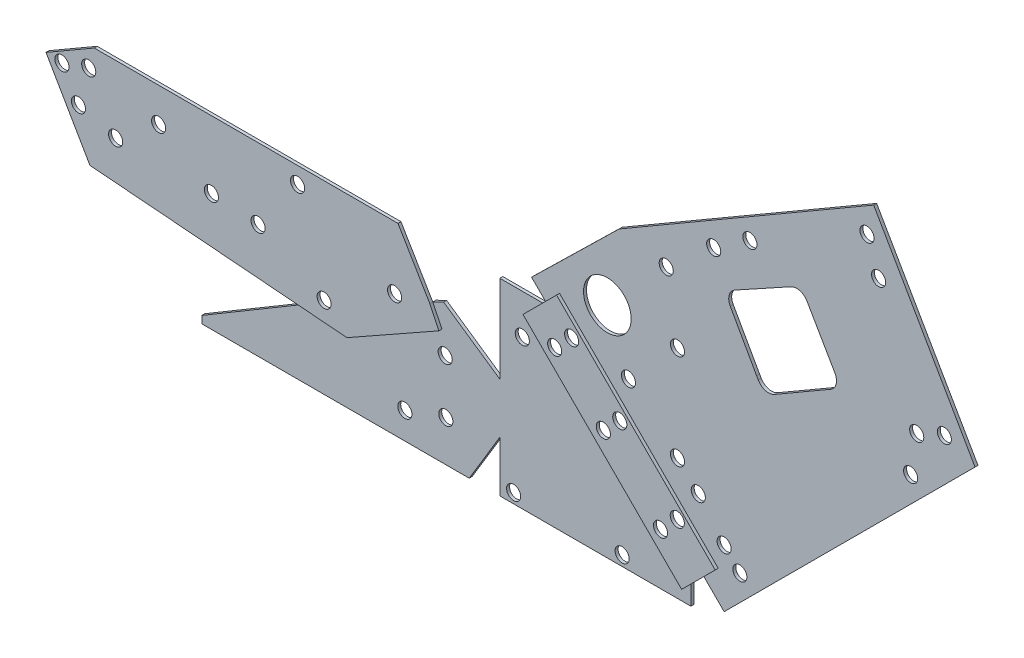
SolidWorks part; units mm, degrees
ref_plane "Plano frontal" through (0, 0, 0) normal (0, 0, 1) x (1, 0, 0)
ref_plane "Plano superior" through (0, 0, 0) normal (0, 1, 0) x (1, 0, 0)
ref_plane "Plano direito" through (0, 0, 0) normal (1, 0, 0) x (0, 0, -1)
sketch "Esboço1" plane through (0, 0, 0) normal (0, 0, 1) x (1, 0, 0)
  line L0 (341.3333, 723.5) -> (1706.6667, 723.5) construction
  line L1 (4933.5577, 4260.6978) -> (5445.3782, 3370.7776)
  line L2 (5445.3782, 3370.7776) -> (4178.4392, 2104.8716)
  line L3 (4178.4392, 2104.8716) -> (4076.0051, 2207.3893)
  line L4 (4076.0051, 2207.3893) -> (4148.4155, 2279.7406)
  line L5 (4148.4155, 2279.7406) -> (3347.2308, 3081.579)
  line L6 (3347.2308, 3081.579) -> (3177.5814, 2912.0679)
  line L7 (3177.5814, 2912.0679) -> (3978.7661, 2110.2295)
  line L8 (3978.7661, 2110.2295) -> (4076.0051, 2207.3893)
  line L9 (3276.4892, 3010.8951) -> (3205.8629, 3081.579)
  line L10 (3205.8629, 3081.579) -> (3647.9072, 3513.3999)
  line L11 (3647.9072, 3513.3999) -> (4100.6528, 3776.9135)
  line L12 (4100.6528, 3776.9135) -> (4933.5577, 4260.6978)
  line L13 (3262.4061, 2996.8235) -> (3045.3808, 2996.8235)
  line L14 (3045.3808, 2996.8235) -> (3045.3808, 2044.886)
  line L15 (3045.3808, 2044.886) -> (4010.5334, 2044.886)
  line L16 (4010.5334, 2044.886) -> (4010.5334, 2141.9709)
  line L17 (2890.9478, 2044.886) -> (3045.3808, 2300.8767)
  line L18 (3045.3808, 2555.7255) -> (2762.0065, 2750.4853)
  line L19 (2762.0065, 2750.4853) -> (2706.993, 2724.0231)
  line L20 (2706.993, 2724.0231) -> (2753.1477, 2628.0699)
  line L21 (2753.1477, 2628.0699) -> (2288.4358, 2365.9015)
  line L22 (2288.4358, 2365.9015) -> (990.6315, 2470.3434)
  line L23 (990.6315, 2470.3434) -> (768.8685, 2853.6686)
  line L24 (768.8685, 2853.6686) -> (1012.6244, 2994.6873)
  line L25 (1012.6244, 2994.6873) -> (2546.3196, 2994.6873)
  line L26 (2546.3196, 2994.6873) -> (2706.993, 2724.0231)
  line L27 (1540.7391, 2044.886) -> (1540.7391, 2081.8221)
  line L28 (1540.7391, 2081.8221) -> (2051.4198, 2384.9756)
  line L29 (1540.7391, 2044.886) -> (2890.9478, 2044.886)
  line L30 (4342.3927, 3218.7645) -> (4216.4124, 3443.6797)
  line L31 (4238.4239, 3541.7347) -> (4515.798, 3694.658)
  line L32 (4596.6793, 3672.1987) -> (4737.9418, 3428.439)
  line L33 (4716.1132, 3346.4419) -> (4432.8719, 3182.2993)
  line L34 (4342.3927, 3218.7645) -> (4350.8749, 3204.1279)
  line L35 (4238.4239, 3541.7347) -> (4232.5399, 3538.4907)
  line L36 (4216.4124, 3443.6797) -> (4209.1608, 3456.626)
  circle A0 centre (3588.5895, 3150.4639) radius 120.3133
  circle A1 centre (4899.7093, 4116.2578) radius 35.6606
  circle A2 centre (4958.2142, 3952.2718) radius 35.6606
  circle A3 centre (5150.8633, 3370.7776) radius 35.6606
  circle A4 centre (5290.3818, 3431.5246) radius 35.6606
  circle A5 centre (5120.2839, 3175.4222) radius 35.6606
  circle A6 centre (4308.3601, 3792.9081) radius 35.6606
  circle A7 centre (4125.661, 3670.6609) radius 35.6606
  circle A8 centre (4257.693, 2313.3917) radius 35.6606
  circle A9 centre (4178.4392, 2396.3217) radius 35.6606
  circle A10 centre (4047.7765, 2555.7255) radius 35.6606
  circle A11 centre (3942.8183, 2659.3652) radius 35.6606
  circle A12 centre (3695.1216, 2881.1287) radius 35.6606
  circle A13 centre (3942.8183, 3140.5478) radius 35.6606
  circle A14 centre (3885.941, 3466.2564) radius 35.6606
  circle A15 centre (3956.7376, 2405.3029) radius 35.6606
  circle A16 centre (3872.0513, 2319.6318) radius 35.6606
  circle A17 centre (3583.4304, 2608.084) radius 35.6606
  circle A18 centre (3666.3262, 2690.9798) radius 35.6606
  circle A19 centre (3337.5538, 2847.9017) radius 35.6606
  circle A20 centre (3423.381, 2932.3447) radius 35.6606
  circle A21 centre (3159.0283, 2796.0426) radius 35.6606
  circle A22 centre (3115.3836, 2094.8055) radius 35.6606
  circle A23 centre (3663.3337, 2096.1195) radius 35.6606
  circle A24 centre (2565.9127, 2179.6694) radius 35.6606
  circle A25 centre (2769.7856, 2520.4665) radius 35.6606
  circle A26 centre (2772.8644, 2251.0772) radius 35.6606
  circle A27 centre (2173.1952, 2472.0856) radius 35.6606
  circle A28 centre (2529.1931, 2678.1099) radius 35.6606
  circle A29 centre (1604.09, 2654.1286) radius 35.6606
  circle A30 centre (1839.8326, 2636.6662) radius 35.6606
  circle A31 centre (2039.3115, 2911.4571) radius 35.6606
  circle A32 centre (1120.5017, 2654.4881) radius 35.6606
  circle A33 centre (1337.6956, 2822.5846) radius 35.6606
  circle A34 centre (984.5932, 2893.1951) radius 35.6606
  circle A35 centre (849.4236, 2847.1799) radius 35.6606
  circle A36 centre (932.8261, 2706.2585) radius 35.6606
  arc A37 (4350.8749, 3204.1279) -> (4432.8719, 3182.2993) centre (4402.7877, 3234.2121) ccw
  arc A38 (4737.9418, 3428.439) -> (4716.1132, 3346.4419) centre (4686.029, 3398.3547) cw
  arc A39 (4596.6793, 3672.1987) -> (4515.798, 3694.658) centre (4544.7665, 3642.1145) ccw
  arc A40 (4209.1608, 3456.626) -> (4232.5399, 3538.4907) centre (4261.5084, 3485.9472) cw
  point P116 (4380.9591, 3152.2151)
  dimension "D28" = 60
  dimension "D1" = 1026.6052
  dimension "D2" = 1790.992
  dimension "D3" = 144.9228
  dimension "D4" = 99.9215
  dimension "D5" = 617.9583
  dimension "D6" = 239.8227
  dimension "D7" = 1133.5086
  dimension "D8" = 523.8492
  dimension "D9" = 963.2122
  dimension "D10" = 217.0253
  dimension "D11" = 951.9375
  dimension "D12" = 965.1526
  dimension "D13" = 97.085
  dimension "D14" = 298.9663
  dimension "D15" = 343.8494
  dimension "D16" = 61.047
  dimension "D17" = 106.4767
  dimension "D18" = 533.563
  dimension "D19" = 1302
  dimension "D20" = 442.8511
  dimension "D21" = 281.6083
  dimension "D22" = 1533.6952
  dimension "D23" = 314.7619
  dimension "D24" = 36.9362
  dimension "D25" = 593.8829
  dimension "D26" = 1350.2087
  dimension "D27" = 257.7943
extrude "Ressalto-extrusão1" add sketch "Esboço1" along normal blind 15 contours L7 L8 L4 L5 L6 A20 A19 A18 A17 A16 A15 region at (3665.2309, 2592.2162, 0)
extrude "Ressalto-extrusão2" add sketch "Esboço1<3>" against normal blind 15 separate body contours L12 L11 L10 L9 L6 L5 L4 L3 L2 L1 A14 A13 A12 A11 A10 A9 A8 A7 A6 A5 A4 A3 A2 A1 A0 L36 A40 L35 L31 A39 L32 A38 L33 A37 L34 | L15 L16 L8 L7 L6 L13 L14 A23 A22 A21 | L27 L29 L17 L14 L18 L19 L20 L21 L22 L28 A26 A25 A24 region at (5162.5213, 3800.2399, 0) region at (3378.2113, 2386.2015, 0) region at (2463.1151, 2278.2783, 0)
sketch "Esboço1<3>" plane through (0, 0, 0) normal (0, 0, 1) x (1, 0, 0) same geometry as "Esboço1"
extrude "Ressalto-extrusão3" add sketch "Esboço1<4>" along normal blind 15 separate body contours L26 L25 L24 L23 L22 L21 L20 A36 A35 A34 A33 A32 A31 A30 A29 A28 A27 region at (1784.0327, 2710.2166, 0)
sketch "Esboço1<4>" plane through (0, 0, 0) normal (0, 0, 1) x (1, 0, 0) same geometry as "Esboço1"
